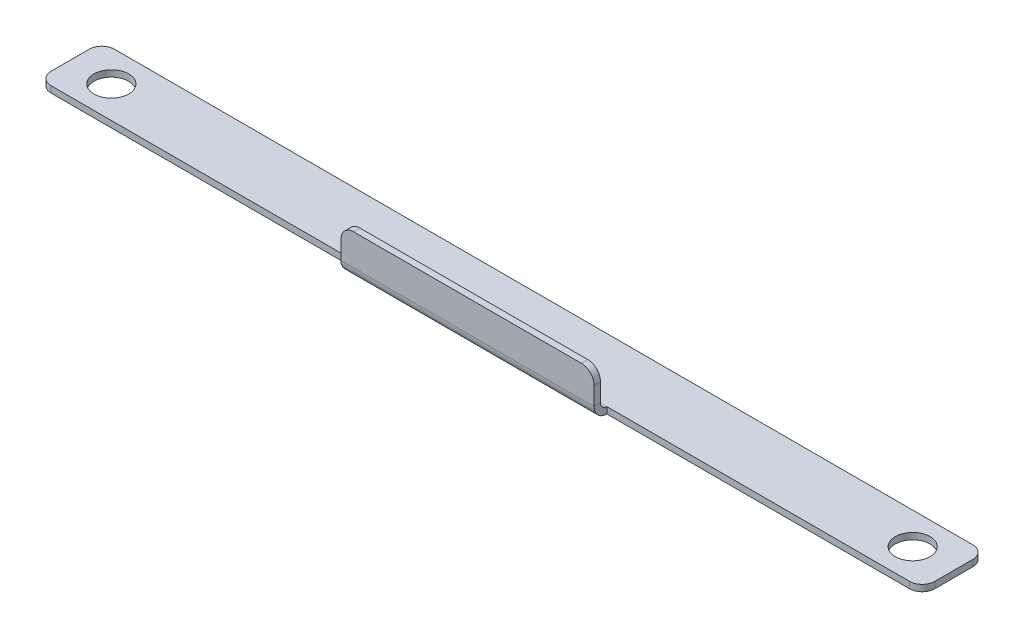
SolidWorks part; units mm, degrees
note: The reader was unsure of these and kept them because the rebuilt part matched: thickness of "Base-Flange1", "Edge-Flange1", "Sheet-Metal1", "Sheet-Metal2", "Sheet-Metal3"; flange length of "Edge-Flange1".
ref_plane "Front Plane" through (0, 0, 0) normal (0, 0, 1) x (1, 0, 0)
ref_plane "Top Plane" through (0, 0, 0) normal (0, 1, 0) x (1, 0, 0)
ref_plane "Right Plane" through (0, 0, 0) normal (1, 0, 0) x (0, 0, -1)
sketch "Sketch1" plane through (0, 0, 0) normal (0, 1, 0) x (1, 0, 0)
  line L1 (-126.8505, 10) -> (12.7995, 10)
  line L2 (-126.8505, 10) -> (-126.8505, 0)
  line L3 (-126.8505, 0) -> (12.7995, 0)
  line L4 (12.7995, 10) -> (12.7995, 0)
  line L10 (-126.8505, 274.468) -> (-126.8505, -33.532) construction
  line L12 (12.7995, -33.532) -> (12.7995, 274.468) construction
  dimension "D1" = 10
base flange "Base-Flange1" sketch "Sketch1" thickness 1.016 reverse thickness direction no parameters "D1"=3.048
edge flange "Edge-Flange1" sketch "Sketch8" flange angle 90 flange length 5.94 flange position bend outside bend radius 1.016 thickness 1.016 relief rectangular parameters "D6"=10
sketch "Sketch8" plane through (0, 0, 0) normal (0, 0, 1) x (1, 0, 0)
  line L0 (-126.8505, 0) -> (12.7995, 0) construction
  line L1 (-77.0255, 0) -> (-37.0255, 0)
  line L2 (-77.0255, 0) -> (-77.0255, 5.94)
  line L3 (-77.0255, 5.94) -> (-37.0255, 5.94)
  line L4 (-37.0255, 5.94) -> (-37.0255, 0)
  point P6 (-57.0255, 0)
  point P7 (-57.0255, 0)
  dimension "D1" = 40
bend "EdgeBend1" bend radius 1.016 bend angle 90 parameters "D5"=1
fillet "Fillet1" radius 2 6 edges at (-126.8505, -0.508, -10) (-126.8505, -0.508, 0) (12.7995, -0.508, -10) (12.7995, -0.508, 0) (-77.0255, 5.94, 1.524) (-37.0255, 5.94, 1.524)
sketch "Sketch9" plane through (0, 0, 0) normal (0, 1, 0) x (1, 0, 0)
  line L0 (-126.8505, 5) -> (-120.3505, 5) construction
  line L1 (-126.8505, 8) -> (-126.8505, 2) construction
  line L2 (12.7995, 5) -> (6.2995, 5) construction
  line L3 (12.7995, 2) -> (12.7995, 8) construction
  dimension "D1" = 6.5
hole_wizard "M5 Clearance Hole1" positions "Sketch10" profile "Sketch11" hole size "M5" standard "ANSI Metric" end condition through all
sketch "Sketch10" plane through (0, 0, 0) normal (0, 1, 0) x (1, 0, 0)
  point P0 (-120.3505, 5)
  point P4 (6.2995, 5)
sketch "Sketch11" plane through (-120.3505, 0, -5) normal (1, 0, 0) x (0, 0, 1)
  line L0 (0, 0) -> (0, 1.016)
  line L1 (0, 1.016) -> (2.75, 1.016)
  line L2 (2.75, 1.016) -> (2.75, 0)
  line L5 (2.75, 0) -> (0, 0)
  line L11 (0, -6.35) -> (0, 107.95) construction
  dimension "Thru Hole Dia." = 5.5
  dimension "Thru Hole Depth" = 1.016
sketch "Bend-Lines1" [suppressed] plane through (0, 0, 0) normal (0, 1, 0) x (1, 0, 0)
sketch "Bounding-Box1" [suppressed] plane through (0, 0, 0) normal (0, 1, 0) x (1, 0, 0)
sheet metal parameters "Sheet-Metal1" thickness 1.016 parameters "D1"=3.048, "D7"=2.032
flat pattern "Flat-Pattern1" [suppressed]
sketch "Bend-Lines2" plane through (0, 0, 0) normal (0, 1, 0) x (1, 0, 0)
sketch3d "Bounding-Box2" [suppressed]
  line L0 (-14.7618, 0.0001, 0) -> (125.0782, 0, 0) construction
  line L1 (-14.7618, 6.75, 0) -> (125.0782, 6.7499, 0) construction
  line L2 (-14.7618, 0.0001, 0) -> (-14.7618, 6.75, 0) construction
  line L3 (125.0782, 0, 0) -> (125.0782, 6.7499, 0) construction
sheet metal parameters "Sheet-Metal2" thickness 1.016 parameters "D1"=3.048, "D7"=2.032
flat pattern "Flat-Pattern1"
sketch "Bend-Lines2" plane through (0, 0, 0) normal (0, 1, 0) x (1, 0, 0)
  line L0 (35.1582, -1.1969) -> (75.1582, -1.1969) construction
  line L1 (35.1582, -1.1969) -> (75.1582, -1.1969) construction
sketch3d "Bounding-Box2" [suppressed]
  line L0 (-14.7618, -11.4578, 0) -> (125.0782, -11.4579, 0) construction
  line L1 (-14.7618, 6.75, 0) -> (125.0782, 6.7499, 0) construction
  line L2 (-14.7618, -11.4578, 0) -> (-14.7618, 6.75, 0) construction
  line L3 (125.0782, -11.4579, 0) -> (125.0782, 6.7499, 0) construction
bend of the flat pattern "Flatten-<EdgeBend1>1"
sheet metal parameters "Sheet-Metal3" thickness 1.016 parameters "D1"=3.048, "D7"=2.032
flat pattern "Flat-Pattern1"
sketch "Bend-Lines2" plane through (0, 0, 0) normal (0, 1, 0) x (1, 0, 0)
  line L0 (-77.0255, -1.1969) -> (-37.0255, -1.1969) construction
  line L1 (-77.0255, -1.1969) -> (-37.0255, -1.1969) construction
sketch3d "Bounding-Box2" [suppressed]
  line L0 (-126.8505, -7.3178, 0) -> (12.7995, -7.3179, 0) construction
  line L1 (-126.8505, 10, 0) -> (12.7995, 9.9999, 0) construction
  line L2 (-126.8505, -7.3178, 0) -> (-126.8505, 10, 0) construction
  line L3 (12.7995, -7.3179, 0) -> (12.7995, 9.9999, 0) construction
bend of the flat pattern "Flatten-<EdgeBend1>1"
